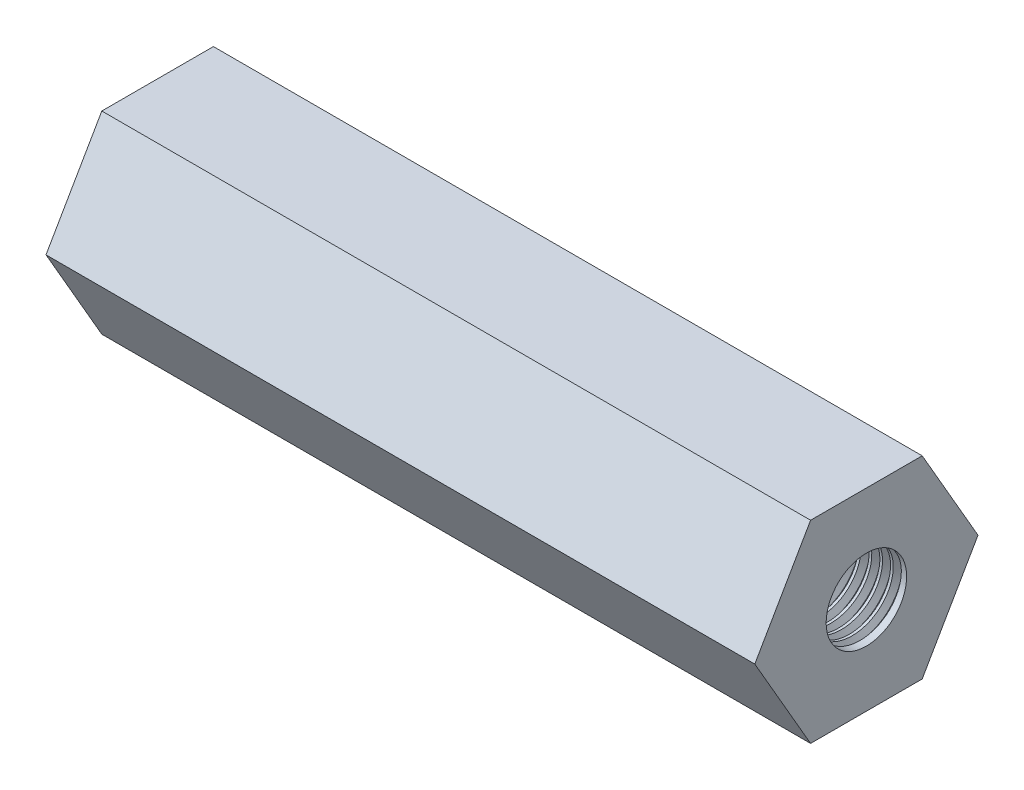
SolidWorks part; units mm, degrees
ref_plane "Front Plane" through (0, 0, 0) normal (0, 0, 1) x (1, 0, 0)
ref_plane "Top Plane" through (0, 0, 0) normal (0, 1, 0) x (1, 0, 0)
ref_plane "Right Plane" through (0, 0, 0) normal (1, 0, 0) x (0, 0, -1)
sketch "Sketch2" plane through (0, 0, 0) normal (1, 0, 0) x (0, 0, -1)
  line L0 (0, 0) -> (10.9985, 0) construction
  line L1 (10.9985, 0) -> (5.4993, 9.525)
  line L2 (5.4993, 9.525) -> (-5.4993, 9.525)
  line L3 (-5.4993, 9.525) -> (-10.9985, 0)
  line L4 (-10.9985, 0) -> (-5.4993, -9.525)
  line L5 (-5.4993, -9.525) -> (5.4993, -9.525)
  line L6 (5.4993, -9.525) -> (10.9985, 0)
  circle A0 centre (0, 0) radius 3.9688
  circle A1 centre (0, 0) radius 9.525 construction
  dimension "D1" = 7.9375
  dimension "D2" = 19.05
extrude "Boss-Extrude1" add sketch "Sketch2" along normal mid plane 69.85
thread "Thread1" pitch 1.0583 profile "Thread Profile1" start angle 0, offset 0, length 31.75, pitch 1.0583, diameter 7.9375
ref_plane "Plane1" through (34.925, 0, 3.9688) normal (0, -1, 0) x (0, 0, 1)
sketch "Thread Profile1" plane through (34.925, 0, 3.9688) normal (0, -1, 0) x (0, 0, 1)
  line L0 (0, 0) -> (0, 1.0583) construction
  line L1 (0, 0) -> (0.5728, 0.3307)
  line L2 (0.5728, 0.3307) -> (0.5728, 0.463)
  line L3 (0.5728, 0.463) -> (0, 0.7937)
  line L4 (0.5728, 0.3969) -> (0, 0.3969) construction
  line L11 (0, 0) -> (0, 0.7937)
  point P2 (0, 0)
  dimension "Pitch" = 1.0583
  dimension "Profile_Angle" = 60
  dimension "Profile_Land" = 0.1323
  dimension "Profile_Height" = 0.5728
thread "Thread2" start angle 0, offset 0, length 31.75, pitch 1.0583, diameter 7.9375
ref_plane "Plane2" through (-34.925, 0, -3.9688) normal (0, -1, 0) x (0, 0, -1)
sketch "Thread Profile2" plane through (-34.925, 0, -3.9688) normal (0, -1, 0) x (0, 0, -1)
  line L0 (0, 0) -> (0, 1.0583) construction
  line L1 (0, 0) -> (0.5728, 0.3307)
  line L2 (0.5728, 0.3307) -> (0.5728, 0.463)
  line L3 (0.5728, 0.463) -> (0, 0.7937)
  line L4 (0.5728, 0.3969) -> (0, 0.3969) construction
  line L11 (0, 0) -> (0, 0.7937)
  point P2 (0, 0)
  dimension "Pitch" = 1.0583
  dimension "Profile_Angle" = 60
  dimension "Profile_Land" = 0.1323
  dimension "Profile_Height" = 0.5728
